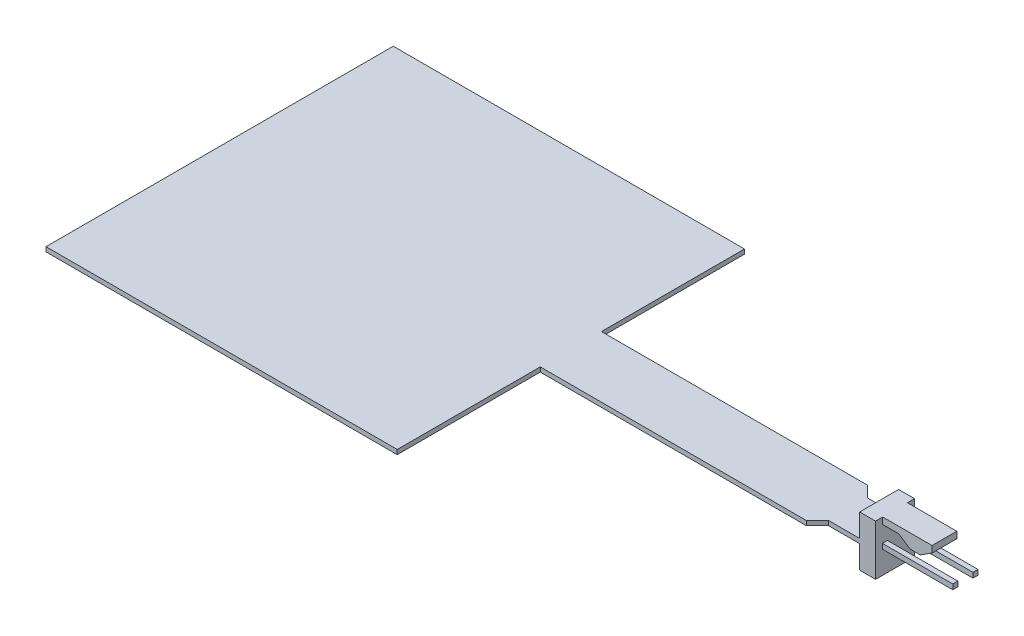
SolidWorks part; units mm, degrees
ref_plane "Front Plane" through (0, 0, 0) normal (0, 0, 1) x (1, 0, 0)
ref_plane "Top Plane" through (0, 0, 0) normal (0, 1, 0) x (1, 0, 0)
ref_plane "Right Plane" through (0, 0, 0) normal (1, 0, 0) x (0, 0, -1)
sketch "Sketch1" plane through (0, 0, 0) normal (0, 1, 0) x (1, 0, 0)
  line L0 (0, 0) -> (55.58, 0) construction
  line L1 (22.1, 3.85) -> (55.58, 3.85)
  line L3 (22.1, -3.85) -> (55.58, -3.85)
  line L4 (55.58, 3.85) -> (55.58, -3.85) construction
  line L5 (22.1, 3.85) -> (22.1, 21.85)
  line L6 (55.58, 3.85) -> (56.98, 2.45)
  line L7 (56.98, 2.45) -> (60.9, 2.45)
  line L8 (60.9, 2.45) -> (60.9, -2.45)
  line L9 (60.9, -2.45) -> (56.98, -2.45)
  line L10 (56.98, -2.45) -> (55.58, -3.85)
  line L11 (55.58, 0) -> (60.9, 0) construction
  line L14 (-22.1, -21.85) -> (22.1, -21.85)
  line L15 (-22.1, -21.85) -> (-22.1, 21.85)
  line L16 (-22.1, 21.85) -> (22.1, 21.85)
  line L17 (22.1, -21.85) -> (22.1, -3.85)
  line L18 (-22.1, -21.85) -> (22.1, 21.85) construction
  line L19 (-22.1, 21.85) -> (22.1, -21.85) construction
  point P7 (56.9213, -2.45)
  point P19 (0, 0)
  point P20 (0, 0)
  dimension "D1" = 83
  dimension "D3" = 43.7
  dimension "D2" = 7.7
  dimension "D4" = 4.9
  dimension "D5" = 45
  dimension "D6" = 44.2
  dimension "D7" = 5.32
extrude "Boss-Extrude1" add sketch "Sketch1" along normal mid plane 0.57
sketch "Sketch2" plane through (60.9, 0, 0) normal (1, 0, 0) x (0, 0, -1)
  line L0 (-2.45, -3.175) -> (2.45, 3.175) construction
  line L1 (-2.45, -3.175) -> (2.45, -3.175)
  line L2 (-2.45, -3.175) -> (-2.45, 3.175)
  line L3 (-2.45, 3.175) -> (2.45, 3.175)
  line L4 (2.45, -3.175) -> (2.45, 3.175)
  point P4 (0, 0)
  dimension "D1" = 6.35
  dimension "D2" = 4.9
extrude "Boss-Extrude2" add sketch "Sketch2" along normal blind 2
sketch "Sketch3" plane through (0, 0, 0) normal (0, 0, 1) x (1, 0, 0)
  line L0 (62.9, 3.175) -> (69.11, 3.175)
  line L1 (69.11, 3.175) -> (69.11, 2.355)
  line L2 (69.11, 2.355) -> (67.63, 1.405)
  line L3 (67.63, 1.405) -> (66.38, 1.405)
  line L4 (66.38, 1.405) -> (64.9, 2.355)
  line L5 (64.9, 2.355) -> (62.9, 2.355)
  line L6 (62.9, 3.175) -> (62.9, -3.175) construction
  line L7 (62.9, 2.355) -> (62.9, 3.175)
  line L8 (60.9, 3.175) -> (60.9, 0.285) construction
  line L9 (64.9, 2.355) -> (69.11, 2.355) construction
  line L10 (67.005, 1.405) -> (67.005, 2.355) construction
  dimension "D1" = 8.21
  dimension "D2" = 0.82
  dimension "D3" = 1.77
  dimension "D4" = 2
  dimension "D5" = 1.25
extrude "Boss-Extrude3" add sketch "Sketch3" along normal mid plane 3.11
sketch "Sketch4" plane through (62.9, 0, 0) normal (1, 0, 0) x (0, 0, -1)
  line L0 (-2.45, 0) -> (2.45, 0) construction
  line L1 (2.45, 0.285) -> (2.45, -0.285) construction
  line L2 (-0.9525, -0.3175) -> (0.9525, -0.3175) construction
  line L3 (-1.5875, -0.3175) -> (-0.9525, -0.3175)
  line L4 (-1.5875, -0.3175) -> (-1.5875, 0.3175)
  line L5 (-1.5875, 0.3175) -> (-0.9525, 0.3175)
  line L6 (-0.9525, -0.3175) -> (-0.9525, 0.3175)
  line L7 (-1.5875, -0.3175) -> (-0.9525, 0.3175) construction
  line L8 (-1.5875, 0.3175) -> (-0.9525, -0.3175) construction
  line L9 (0.9525, -0.3175) -> (1.5875, -0.3175)
  line L10 (0.9525, -0.3175) -> (0.9525, 0.3175)
  line L11 (0.9525, 0.3175) -> (1.5875, 0.3175)
  line L12 (1.5875, -0.3175) -> (1.5875, 0.3175)
  line L13 (0.9525, -0.3175) -> (1.5875, 0.3175) construction
  line L14 (0.9525, 0.3175) -> (1.5875, -0.3175) construction
  line L15 (0, 0) -> (0, -0.3175) construction
  point P0 (-1.27, 0)
  point P6 (0, 0)
  point P12 (1.27, 0)
  dimension "D1" = 0.635
  dimension "D2" = 2.54
extrude "Boss-Extrude4" add sketch "Sketch4" along normal offset from surface (8.85 mm away) 10.85 up to face at (60.9, 1.73, 0)
